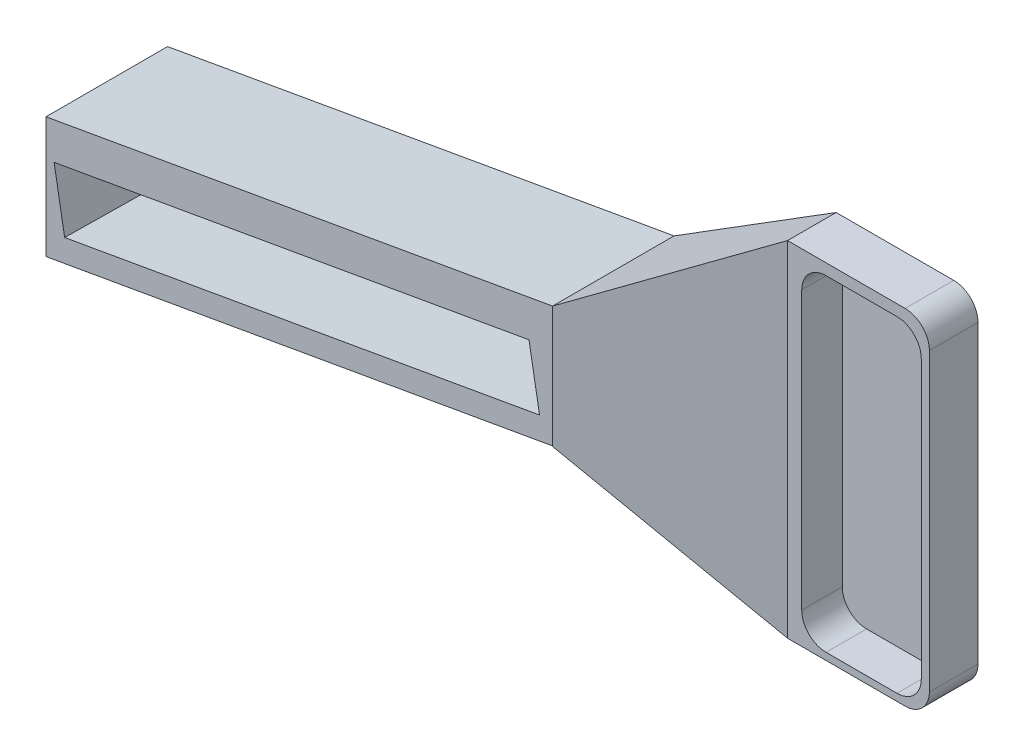
SolidWorks part; units mm, degrees
ref_plane "Plan de face" through (0, 0, 0) normal (0, 0, 1) x (1, 0, 0)
ref_plane "Plan de dessus" through (0, 0, 0) normal (0, 1, 0) x (1, 0, 0)
ref_plane "Plan de droite" through (0, 0, 0) normal (1, 0, 0) x (0, 0, -1)
sketch "Esquisse1" plane through (0, 0, 0) normal (0, 0, 1) x (1, 0, 0)
  line L1 (0, 0) -> (200, 0)
  line L2 (0, 0) -> (0, 85)
  line L3 (0, 85) -> (200, 85)
  line L4 (200, 0) -> (200, 85)
  dimension "D1" = 200
  dimension "D2" = 85
extrude "Boss.-Extru.1" add sketch "Esquisse1" along normal blind 30
sketch "Esquisse2" plane through (0, 0, 30) normal (0, 0, 1) x (1, 0, 0)
  line L0 (200, 90) -> (0, 54.7346)
  line L1 (2, 29.2219) -> (4.6047, 14.4498)
  line L2 (2, 29.2219) -> (119.1921, 49.8861)
  line L3 (4.6047, 14.4498) -> (121.7968, 35.1139)
  line L4 (119.1921, 49.8861) -> (121.7968, 35.1139)
  line L5 (0, 85) -> (0, 0) construction
  line L6 (0, 0) -> (200, 0) construction
  line L7 (200, 0) -> (200, 85) construction
  point P6 (3.3024, 21.8359)
  point P7 (120.4945, 42.5)
  dimension "D1" = 119
  dimension "D2" = 15
  dimension "D3" = 10
  dimension "D4" = 42.5
  dimension "D5" = 2
  dimension "D6" = 15
  dimension "D7" = 0
  dimension "D8" = 5
extrude "Enlèv. mat.-Extru.3" cut sketch "Esquisse2" against normal blind 28 contours L4 L2 L1 L3 region at (61.8984, 32.1679, 30)
sketch "Esquisse3" plane through (0, 0, 30) normal (0, 0, 1) x (1, 0, 0)
  line L0 (0, 0) -> (200, 0) construction
  line L1 (200, 85) -> (165, 85)
  line L2 (200, 85) -> (200, 0)
  line L3 (200, 0) -> (165, 0)
  line L4 (165, 85) -> (165, 0)
  dimension "D1" = 35
extrude "Enlèv. mat.-Extru.4" cut sketch "Esquisse3" against normal blind 18
sketch "Esquisse4" plane through (0, 0, 12) normal (0, 0, 1) x (1, 0, 0)
  line L0 (200, 0) -> (200, 85) construction
  line L1 (198, 82.25) -> (168.5, 82.25)
  line L2 (198, 82.25) -> (198, 1.75)
  line L3 (198, 1.75) -> (168.5, 1.75)
  line L4 (168.5, 82.25) -> (168.5, 1.75)
  line L5 (165, 0) -> (200, 0) construction
  dimension "D1" = 2
  dimension "D2" = 80.5
  dimension "D3" = 1.75
  dimension "D4" = 29.5
extrude "Enlèv. mat.-Extru.5" cut sketch "Esquisse4" against normal blind 10
chamfer "Chanfrein1" distance 40 distance2 18 1 edges at (165, 42.5, 30) first distance on face at (82.5, 42.5, 30)
sketch "Esquisse7" plane through (0, 0, 30) normal (0, 0, 1) x (1, 0, 0)
  line L0 (125, 60) -> (0, 37.9591)
  line L1 (125, 0) -> (125, 85) construction
  line L2 (0, 85) -> (0, 0) construction
  line L3 (2, 29.2219) -> (119.1921, 49.8861) construction
  line M3 (125, 0) -> (125, 85)
  line M4 (125, 85) -> (0, 85)
  line M5 (0, 85) -> (0, 0)
  dimension "D1" = 0
  dimension "D2" = 25
extrude "Enlèv. mat.-Extru.18" cut sketch "Esquisse7" against normal through all contours L0 M3 M4 M5 region at (56.1261, 66.4278, 30)
sketch "Esquisse9" plane through (0, 0, 30) normal (0, 0, 1) x (1, 0, 0)
  line L0 (0, 8.0731) -> (125, 30.1139)
  line L1 (0, 37.9591) -> (0, 0) construction
  line L2 (125, 0) -> (125, 60) construction
  line L3 (4.6047, 14.4498) -> (121.7968, 35.1139) construction
  line M7 (0, 37.9591) -> (0, 0)
  line M8 (0, 0) -> (125, 0)
  line M9 (125, 0) -> (125, 60)
  dimension "D1" = 0
  dimension "D2" = 5
extrude "Enlèv. mat.-Extru.19" cut sketch "Esquisse9" against normal through all contours L0 M7 M8 M9 region at (74.5246, 10.6069, 30)
chamfer "Chanfrein5" distance 40 distance2 30 1 edges at (125, 0, 15) first distance on face at (163, 0, 10.8)
chamfer "Chanfrein6" distance 25 distance2 40 1 edges at (125, 85, 15) first distance on face at (125, 72.5, 15)
sketch "Esquisse10" plane through (-1.3806, 7.8296, 0) normal (0.1736, -0.9848, 0) x (0.9848, 0.1736, 0)
  line L0 (1.4019, 0) -> (128.3302, 0) construction
  line L1 (6.4019, 2) -> (46.4019, 2)
  line L2 (6.4019, 2) -> (6.4019, 4)
  line L3 (6.4019, 4) -> (46.4019, 4)
  line L4 (46.4019, 2) -> (46.4019, 4)
  line L5 (1.4019, 0) -> (1.4019, 30) construction
  dimension "D1" = 40
  dimension "D2" = 2
  dimension "D3" = 2
  dimension "D4" = 5
extrude "Enlèv. mat.-Extru.20" cut sketch "Esquisse10" against normal blind 2
sketch "Esquisse11" plane through (0, 0, 0) normal (0, 0, -1) x (-1, 0, 0)
  line L0 (-5, 10.9856) -> (-44.3923, 17.9315)
  line L1 (-5, 10.9856) -> (-4.6527, 12.9552)
  line L2 (-44.3923, 17.9315) -> (-44.045, 19.9011)
  line L3 (-4.6527, 12.9552) -> (-44.045, 19.9011)
  line L4 (0, 8.0731) -> (-125, 30.1139) construction
  line L6 (0, 37.9591) -> (0, 8.0731) construction
  dimension "D1" = 40
  dimension "D2" = 2
  dimension "D3" = 0
  dimension "D4" = 2
  dimension "D5" = 5
extrude "Enlèv. mat.-Extru.21" cut sketch "Esquisse11" against normal blind 4
fillet "Congé6" radius 6 4 edges at (198, 1.75, 7) (168.5, 1.75, 7) (198, 82.25, 7) (168.5, 82.25, 7)
fillet "Congé7" radius 6 2 edges at (200, 85, 6) (200, 0, 6)
chamfer "Chanfrein7" distance 119 distance2 2 1 edges at (120.4945, 42.5, 2) first distance on face at (61.8984, 32.1679, 2)
chamfer "Chanfrein8" distance 28 distance2 0.47 1 edges at (3.3024, 21.8359, 2) first distance on face at (3.3024, 21.8359, 16)
